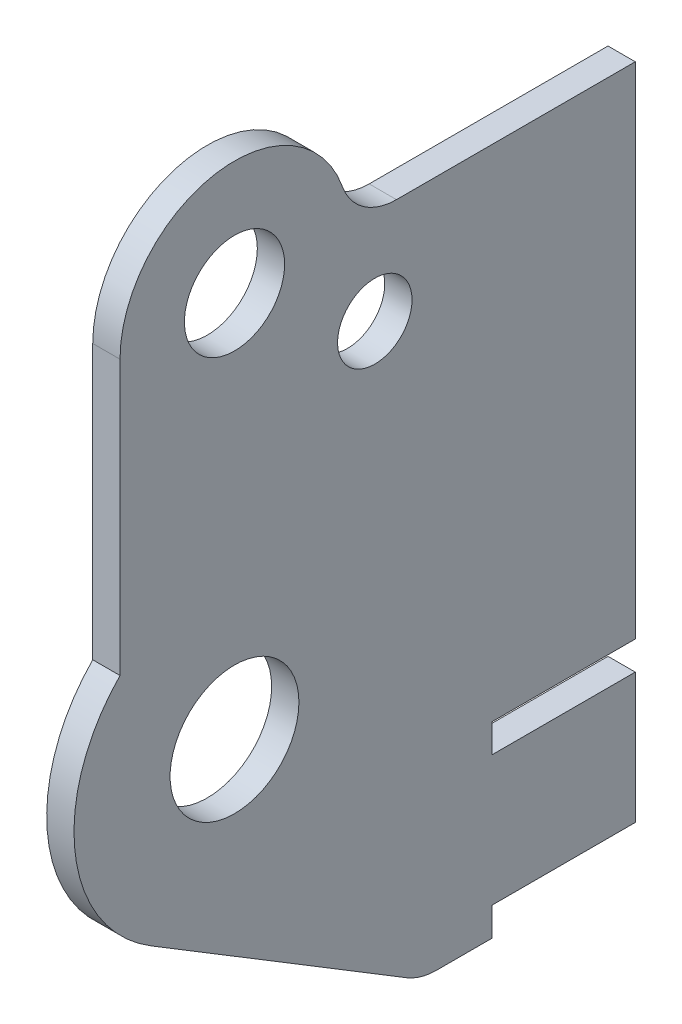
SolidWorks part; units mm, degrees
material "AISI 1020"
ref_plane "Plano frontal" through (0, 0, 0) normal (0, 0, 1) x (1, 0, 0)
ref_plane "Plano superior" through (0, 0, 0) normal (0, 1, 0) x (1, 0, 0)
ref_plane "Plano direito" through (0, 0, 0) normal (1, 0, 0) x (0, 0, -1)
sketch "Esboço1" plane through (0, 0, 0) normal (1, 0, 0) x (0, 0, -1)
  line L0 (0, 0) -> (0, -135) construction
  line L1 (-40, 0) -> (-40, -95.6939)
  line L3 (140, 0) -> (140, -174.65)
  line L4 (140, -174.65) -> (90, -174.65)
  line L5 (90, -174.65) -> (90, -184.65)
  line L6 (90, -184.65) -> (140, -184.65)
  line L7 (140, -184.65) -> (140, -230.15)
  line L8 (140, -230.15) -> (90, -230.15)
  line L9 (90, -230.15) -> (90, -240.15)
  line L10 (90, -240.15) -> (70.6027, -240.15)
  line L11 (60.2127, -237.2394) -> (-29.1336, -182.9187)
  line L12 (56.5685, 0) -> (140, 0)
  circle A0 centre (0, 0) radius 17.5
  circle A1 centre (0, -135) radius 22.5
  arc A2 (37.7124, 13.3333) -> (-40, 0) centre (0, 0) ccw
  arc A3 (-40, -95.6939) -> (-29.1336, -182.9187) centre (0, -135) ccw
  circle A4 centre (49.01, -33) radius 13
  arc A5 (70.6027, -240.15) -> (60.2127, -237.2394) centre (70.6027, -220.15) cw
  arc A6 (37.7124, 13.3333) -> (56.5685, 0) centre (56.5685, 20) ccw
  point P22 (65, -240.15)
  dimension "D2" = 35
  dimension "D3" = 45
  dimension "D4" = 80
  dimension "D5" = 112.16
  dimension "D13" = 26
  dimension "D15" = 33
  dimension "D16" = 20
  dimension "D1" = 135
  dimension "D6" = 140
  dimension "D7" = 174.65
  dimension "D8" = 50
  dimension "D9" = 10
  dimension "D10" = 45.5
  dimension "D11" = 10
  dimension "D12" = 25
  dimension "D14" = 49.01
base flange "Flange-base1" sketch "Esboço1" thickness 9.53 reverse thickness direction no parameters "D1"=0.7366
sketch "Curva-Linhas1" [suppressed] plane through (0, 0, 0) normal (0, 1, 0) x (1, 0, 0)
sketch "Caixa delimitadora1" [suppressed] plane through (0, 0, 0) normal (0, 1, 0) x (1, 0, 0)
sheet metal parameters "Chapa metálica1" thickness 9.53 parameters "D1"=0.7366
flat pattern "Padrão-Plano1" [suppressed]
sketch "Curva-Linhas2" plane through (0, 0, 0) normal (0, 1, 0) x (1, 0, 0)
sketch3d "Caixa delimitadora2" [suppressed]
  line L0 (-139.981, -240.1555, 0) -> (-140.0032, 39.9889, 0) construction
  line L1 (56.0883, -240.14, 0) -> (56.0662, 40.0044, 0) construction
  line L2 (-139.981, -240.1555, 0) -> (56.0883, -240.14, 0) construction
  line L3 (-140.0032, 39.9889, 0) -> (56.0662, 40.0044, 0) construction
